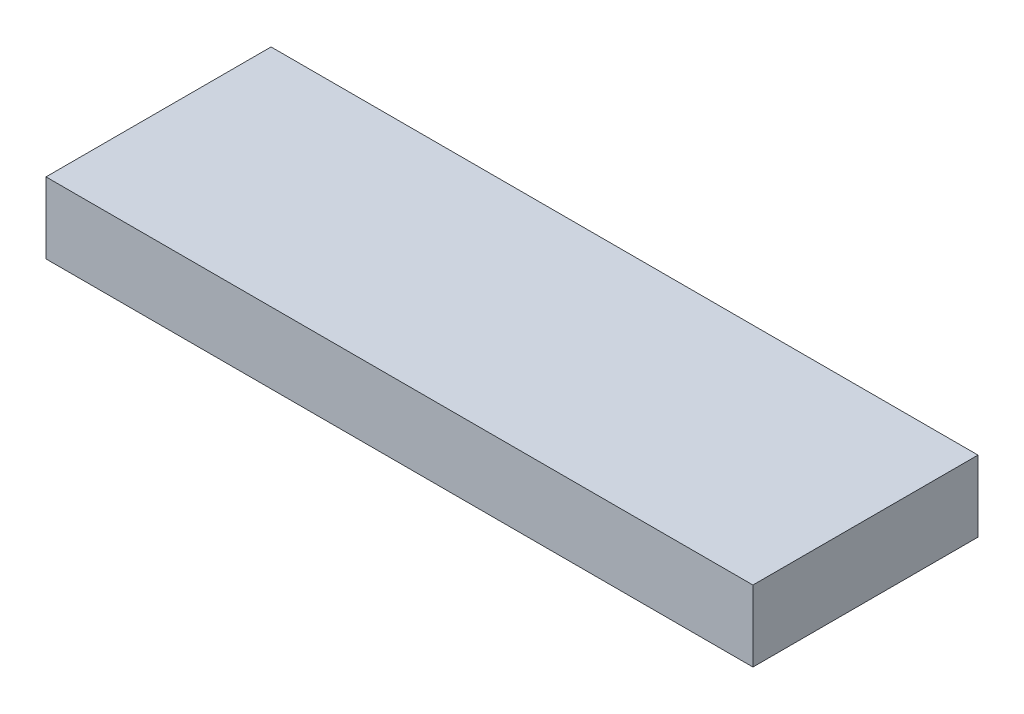
SolidWorks part; units mm, degrees
material "MDF"
ref_plane "Front Plane" through (0, 0, 0) normal (0, 0, 1) x (1, 0, 0)
ref_plane "Top Plane" through (0, 0, 0) normal (0, 1, 0) x (1, 0, 0)
ref_plane "Right Plane" through (0, 0, 0) normal (1, 0, 0) x (0, 0, -1)
sketch "Sketch1" plane through (0, 0, 0) normal (0, 0, 1) x (1, 0, 0)
  line L1 (133.8612, 0) -> (323.3388, 0)
  line L2 (133.8612, 0) -> (133.8612, -19.05)
  line L3 (133.8612, -19.05) -> (323.3388, -19.05)
  line L4 (323.3388, 0) -> (323.3388, -19.05)
  line L5 (323.3388, -298.45) -> (323.3388, 20.8246) construction
  line L6 (133.8612, -298.45) -> (133.8612, 20.8246) construction
  line L8 (456.6888, 0) -> (0.5112, 0) construction
  dimension "D1" = 19.05
extrude "Boss-Extrude1" add sketch "Sketch1" along normal up to surface (60.325 mm away)
hole_wizard "Hole1" positions "Sketch2" profile "Sketch3" legacy
sketch "Sketch2" plane through (228.6, 0, -25.4) normal (0, 0, -1) x (-1, 0, 0)
  line L0 (218.5638, 0) -> (218.5638, -437.642) construction
  line L4 (104.2638, 0) -> (104.2638, -298.45) construction
  line L13 (120.1388, -463.55) -> (120.1388, -311.15) construction
  line L16 (126.4888, -311.15) -> (113.7888, -311.15) construction
  line L18 (126.4888, -304.8) -> (-126.4888, -304.8) construction
  line L22 (94.7388, -276.225) -> (-94.7388, -276.225) construction
  line L24 (-94.7388, -285.75) -> (-94.7388, -266.7) construction
  line L26 (94.7388, -285.75) -> (94.7388, -266.7) construction
  line L27 (-94.7388, 0) -> (-94.7388, -19.05) construction
  line L29 (94.7388, 0) -> (94.7388, -19.05) construction
  line L31 (94.7388, -9.525) -> (-94.7388, -9.525) construction
  point P15 (218.5638, -31.75)
  point P17 (218.5638, -218.821)
  point P19 (218.5638, -418.592)
  point P28 (104.2638, -19.05)
  point P30 (104.2638, -149.225)
  point P32 (104.2638, -279.4)
  point P69 (120.1388, -330.2)
  point P71 (120.1388, -444.5)
  point P76 (-120.1388, -444.5)
  point P77 (-120.1388, -330.2)
  point P80 (-104.2638, -279.4)
  point P81 (-104.2638, -149.225)
  point P82 (-104.2638, -19.05)
  point P83 (-218.5638, -418.592)
  point P84 (-218.5638, -218.821)
  point P85 (-218.5638, -31.75)
  point P99 (0, -304.8)
  point P101 (107.4388, -304.8)
  point P103 (-107.4388, -304.8)
  point P127 (75.6888, -276.225)
  point P129 (0, -276.225)
  point P131 (-75.6888, -276.225)
  point P152 (75.6888, -9.525)
  point P154 (0, -9.525)
  point P156 (-75.6888, -9.525)
sketch "Sketch3" plane through (304.2888, -9.525, -25.4) normal (1, 0, 0) x (0, 1, 0)
  line L0 (0, 0) -> (0, 39.0539)
  line L1 (0, 39.0539) -> (1.5875, 38.1)
  line L2 (1.5875, 38.1) -> (1.5875, 4.0177)
  line L3 (1.5875, 4.0177) -> (5.08, 0)
  line L4 (5.08, 0) -> (0, 0)
  line L5 (0, -14.3089) -> (0, 102.4216) construction
  line L6 (0, 39.0539) -> (-1.5875, 38.1) construction
  line L7 (-1.5875, 4.0177) -> (-5.08, 0) construction
  dimension "Diameter" = 3.175
  dimension "Depth" = 38.1
  dimension "C-Sink Diameter" = 10.16
  dimension "C-Sink Angle" = 82
  dimension "Drill Angle" = 118
